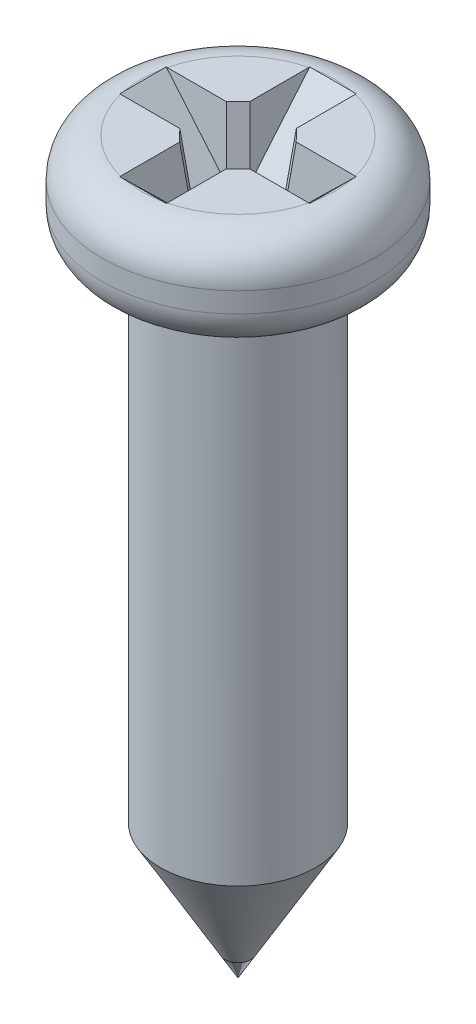
SolidWorks part; units mm, degrees
material "Plain Carbon Steel"
ref_plane "Front Plane" through (0, 0, 0) normal (0, 0, 1) x (1, 0, 0)
ref_plane "Top Plane" through (0, 0, 0) normal (0, 1, 0) x (1, 0, 0)
ref_plane "Right Plane" through (0, 0, 0) normal (1, 0, 0) x (0, 0, -1)
sketch "Sketch1" plane through (0, 0, 0) normal (0, 0, 1) x (1, 0, 0)
  line L0 (0, 9.41) -> (0, 0)
  line L1 (-1, 8.15) -> (-1.75, 8.15)
  line L2 (-1.75, 8.15) -> (-1.75, 9.41)
  line L4 (-1, 8.15) -> (-1, 0)
  line L5 (-1, 0) -> (0, 0)
  line L6 (0, 9.41) -> (-1.75, 9.41)
  dimension "D1" = 2
  dimension "D2" = 9.41
  dimension "D3" = 3.5
  dimension "D4" = 8.15
revolve "Revolve1" add sketch "Sketch1" angle 360 about L0
fillet "Fillet1" radius 0.5 2 edges at (-1.75, 8.15, 0) (-1.75, 9.41, 0)
sketch "Sketch2" plane through (0, 9.41, 0) normal (0, 1, 0) x (1, 0, 0)
  line L1 (-0.3, -1.225) -> (0.3, -1.225)
  line L2 (-0.3, -1.225) -> (-0.3, 1.225)
  line L3 (-0.3, 1.225) -> (0.3, 1.225)
  line L4 (0.3, -1.225) -> (0.3, 1.225)
  line L5 (-0.3, -1.225) -> (0.3, 1.225) construction
  line L6 (-0.3, 1.225) -> (0.3, -1.225) construction
  point P0 (0, 0)
  dimension "D1" = 2.45
  dimension "D2" = 0.6
ref_plane "Plane1" through (0, 8.41, 0) normal (0, 1, 0) x (1, 0, 0)
sketch "Sketch3" plane through (0, 8.41, 0) normal (0, 1, 0) x (1, 0, 0)
  line L1 (0.2, 0.2) -> (-0.2, 0.2)
  line L2 (0.2, 0.2) -> (0.2, -0.2)
  line L3 (0.2, -0.2) -> (-0.2, -0.2)
  line L4 (-0.2, 0.2) -> (-0.2, -0.2)
  line L5 (0.2, 0.2) -> (-0.2, -0.2) construction
  line L6 (0.2, -0.2) -> (-0.2, 0.2) construction
  point P0 (0, 0)
  dimension "D1" = 0.4
chamfer "Chamfer1" distance 1 angle 60 1 edges at (-1, 0, 0)
loft "Cut-Loft1" cut profiles "Sketch2", "Sketch3"
pattern_circular "CirPattern1" count 2 every 90 about axis through (0, 0, 0) along (0, 1, 0) of "Cut-Loft1"
chamfer "Chamfer2" distance 0.15 angle 45 4 edges
